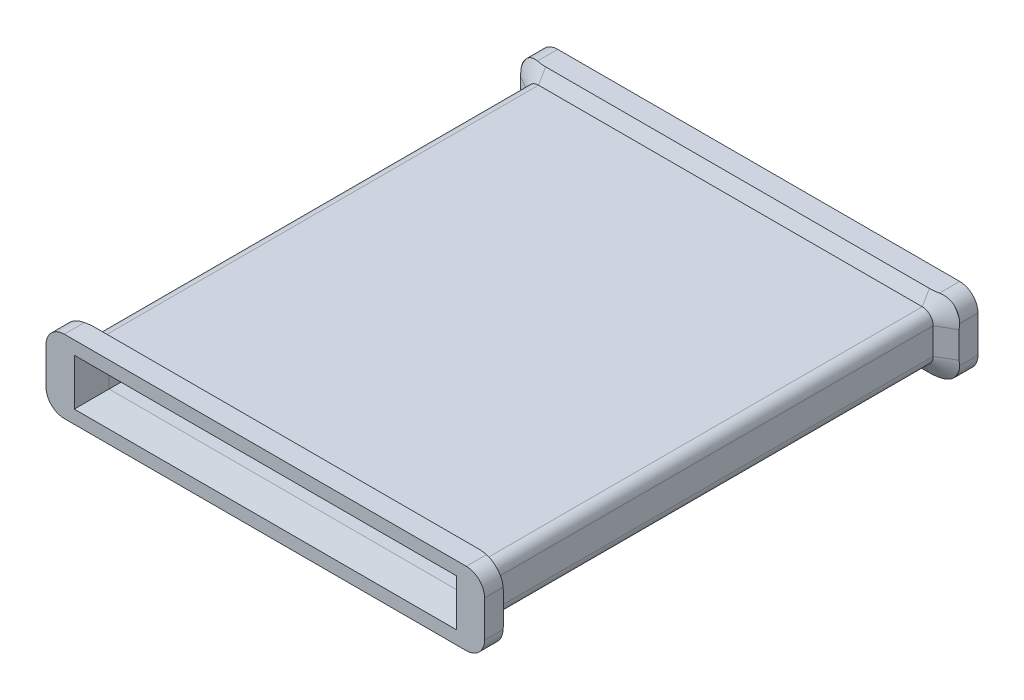
SolidWorks part; units mm, degrees
material "ABS"
ref_plane "Front Plane" through (0, 0, 0) normal (0, 0, 1) x (1, 0, 0)
ref_plane "Top Plane" through (0, 0, 0) normal (0, 1, 0) x (1, 0, 0)
ref_plane "Right Plane" through (0, 0, 0) normal (1, 0, 0) x (0, 0, -1)
sketch "Sketch1" plane through (0, 0, 0) normal (0, 0, 1) x (1, 0, 0)
  line L0 (0, 8) -> (48, 8)
  line L3 (48, 8) -> (48, 0)
  line L4 (48, 0) -> (0, 0)
  line L5 (0, 0) -> (0, 8)
  line L9 (3.4, 6.25) -> (44.6, 6.25)
  line L10 (3.4, 6.25) -> (3.4, 1.75)
  line L11 (3.4, 1.75) -> (44.6, 1.75)
  line L12 (44.6, 6.25) -> (44.6, 1.75)
  dimension "D1" = 1.75
  dimension "D2" = 41.2
  dimension "D4" = 4.5
  dimension "D5" = 1.75
  dimension "D7" = 3.4
  dimension "D8" = 3.4
extrude "Boss-Extrude1" add sketch "Sketch1" along normal blind 54
sketch "Sketch2" plane through (0, 0, 54) normal (0, 0, 1) x (1, 0, 0)
  line L1 (3, 6.65) -> (45, 6.65)
  line L2 (1.8, 5.45) -> (1.8, 2.55)
  line L3 (3, 1.35) -> (45, 1.35)
  line L4 (46.2, 5.45) -> (46.2, 2.55)
  line L5 (3.4, 1.75) -> (44.6, 1.75) construction
  line L6 (44.6, 6.25) -> (3.4, 6.25) construction
  line L8 (3.4, 6.25) -> (3.4, 1.75) construction
  line L9 (44.6, 1.75) -> (44.6, 6.25) construction
  arc A0 (1.8, 2.55) -> (3, 1.35) centre (3, 2.55) ccw
  arc A1 (45, 1.35) -> (46.2, 2.55) centre (45, 2.55) ccw
  arc A2 (45, 6.65) -> (46.2, 5.45) centre (45, 5.45) cw
  arc A3 (3, 6.65) -> (1.8, 5.45) centre (3, 5.45) ccw
  dimension "D1" = 1.2
  dimension "D2" = 0.4
  dimension "D3" = 1.6
  dimension "D4" = 1.6
  dimension "D5" = 0.4
extrude "Cut-Extrude1" cut sketch "Sketch2" against normal offset from surface (50 mm away) 2 from offset 2 flip side to cut up to face at (24, 4, 0) offset against normal yes
fillet "Fillet1" radius 2 8 edges at (48, 8, 53) (48, 0, 53) (48, 0, 1) (48, 8, 1) (0, 0, 1) (0, 8, 1) (0, 0, 53) (0, 8, 53)
chamfer "Chamfer4" distance 1.1 angle 60 16 edges at (1.8, 4, 52) (2.1515, 1.7015, 52) (2.1515, 6.2985, 52) (24, 1.35, 52) (24, 6.65, 52) (45.8485, 1.7015, 52) (45.8485, 6.2985, 52) (46.2, 4, 52) (1.8, 4, 2) (2.1515, 1.7015, 2) (2.1515, 6.2985, 2) (24, 1.35, 2) (24, 6.65, 2) (45.8485, 1.7015, 2) (45.8485, 6.2985, 2) (46.2, 4, 2) first distance on face at (1.8, 4, 27) first distance on face at (2.2757, 1.8257, 27) first distance on face at (2.2757, 6.1743, 27) first distance on face at (24, 1.35, 27) first distance on face at (24, 6.65, 27) first distance on face at (45.7243, 1.8257, 27) first distance on face at (45.7243, 6.1743, 27) first distance on face at (46.2, 4, 27)
chamfer "Chamfer5" distance 3.5 angle 5 8 edges at (44.6, 4, 54) (24, 1.75, 54) (3.4, 4, 54) (24, 6.25, 54) (44.6, 4, 0) (24, 1.75, 0) (3.4, 4, 0) (24, 6.25, 0) first distance on face at (44.6, 4, 27) first distance on face at (24, 1.75, 27) first distance on face at (3.4, 4, 27) first distance on face at (24, 6.25, 27)
